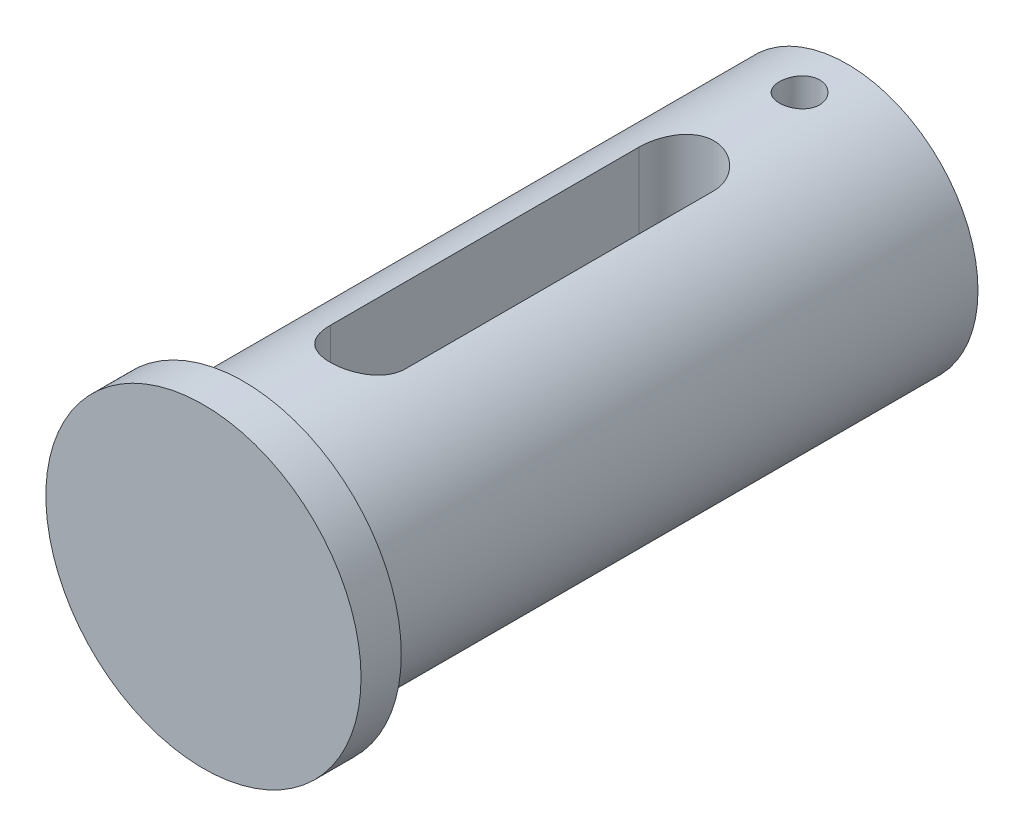
SolidWorks part; units mm, degrees
ref_plane "Front Plane" through (0, 0, 0) normal (0, 0, 1) x (1, 0, 0)
ref_plane "Top Plane" through (0, 0, 0) normal (0, 1, 0) x (1, 0, 0)
ref_plane "Right Plane" through (0, 0, 0) normal (1, 0, 0) x (0, 0, -1)
sketch "Sketch1" plane through (0, 0, 0) normal (0, 0, 1) x (1, 0, 0)
  circle A0 centre (0, 0) radius 9.75
  dimension "D1" = 19.5
extrude "Boss-Extrude1" add sketch "Sketch1" along normal blind 45
sketch "Sketch2" plane through (0, 0, 45) normal (0, 0, 1) x (1, 0, 0)
  circle A0 centre (0, 0) radius 11.75
extrude "Boss-Extrude2" add sketch "Sketch2" along normal blind 3
sketch "Sketch4" plane through (0, 0, 0) normal (0, 1, 0) x (1, 0, 0)
  line L0 (29.5285, -45) -> (-11.75, -45) construction
  line L1 (0, -35.735) -> (23.1721, -35.735) construction
  line L2 (0, -12.735) -> (23.1721, -12.735) construction
  line L3 (0, -38.8025) -> (0, -32.735) construction
  line L5 (0, -38.735) -> (23.1721, -38.735) construction
  line L6 (0, -12.735) -> (0, -35.735) construction
  line L7 (2.8071, -12.735) -> (2.8071, -35.735)
  line L8 (0, -25.735) -> (0, -12.735) construction
  line L9 (-2.8071, -12.735) -> (-2.8071, -35.735)
  arc A1 (2.8071, -12.735) -> (-2.8071, -12.735) centre (0, -12.735) ccw
  arc A2 (-2.8071, -35.735) -> (2.8071, -35.735) centre (0, -35.735) ccw
  point P5 (29.5285, -11.47)
  point P6 (-11.75, -11.47)
  point P14 (0, -24.235)
  dimension "D2" = 23
  dimension "D1" = 3
extrude "Cut-Extrude1" cut sketch "Sketch4" against normal blind 23 and the other way blind 13
sketch "Sketch5" plane through (0, 0, 0) normal (0, 1, 0) x (1, 0, 0)
  line L2 (-20.4017, -2.9601) -> (32.2641, -4.5) construction
  line L3 (0, -3.5566) -> (0, -20.5545) construction
  circle A0 centre (0, -3.5566) radius 1.5
  point P2 (0, 0)
  point P3 (0, -3.5566)
  point P6 (0, 0)
  dimension "D1" = 3
extrude "Cut-Extrude2" cut sketch "Sketch5" against normal blind 23 and the other way blind 23
